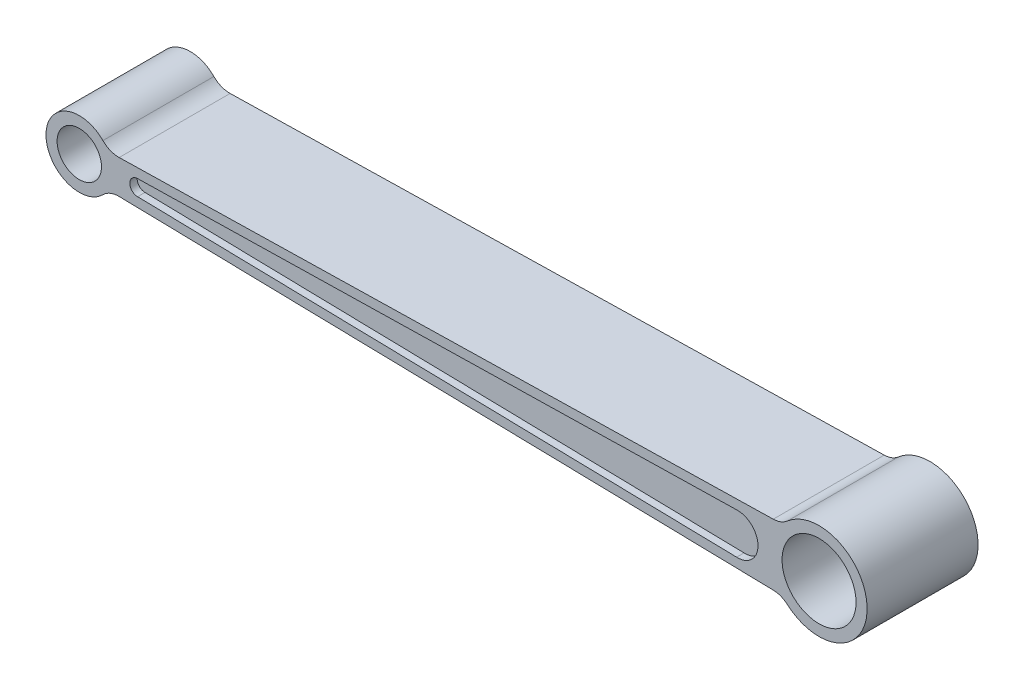
SolidWorks part; units mm, degrees
material "AISI 1020"
ref_plane "Front Plane" through (0, 0, 0) normal (0, 0, 1) x (1, 0, 0)
ref_plane "Top Plane" through (0, 0, 0) normal (0, 1, 0) x (1, 0, 0)
ref_plane "Right Plane" through (0, 0, 0) normal (1, 0, 0) x (0, 0, -1)
sketch "Sketch1" plane through (0, 0, 0) normal (0, 0, 1) x (1, 0, 0)
  line L0 (7.8837, 1.0596) -> (88.9734, 2.7755)
  line L2 (7.8837, -1.0596) -> (88.9734, -2.7755)
  line L5 (3.8971, 2.25) -> (95.0207, 4.1781)
  line L6 (3.8971, -2.25) -> (95.0207, -4.1781)
  circle A0 centre (0, 0) radius 3
  circle A1 centre (0, 0) radius 4.5
  circle A2 centre (100, 0) radius 5
  circle A3 centre (100, 0) radius 6.5
  arc A6 (7.8837, 1.0596) -> (7.8837, -1.0596) centre (7.8837, 0) ccw
  arc A7 (88.856, -2.773) -> (88.856, 2.773) centre (88.9734, 0) ccw
  dimension "D1" = 9
  dimension "D2" = 6
  dimension "D3" = 10
  dimension "D4" = 13
  dimension "D5" = 100
extrude "Boss-Extrude2" add sketch "Sketch1" along normal mid plane 15 contours A3 L5 A1 L6 A7 L2 A6 L0 | A1 A0 | A3 A2 region at (49.4783, 2.2992, 0) region at (4.2237, 1.1317, 0) region at (102.1603, 5.9352, 0)
extrude "Boss-Extrude3" add sketch "Sketch1<7>" along normal mid plane 13 contours L2 A7 L0 A6 region at (55.5485, 0, 0)
sketch "Sketch1<7>" plane through (0, 0, 0) normal (0, 0, 1) x (1, 0, 0) same geometry as "Sketch1"
fillet "Fillet1" radius 3 4 edges at (95.0207, -4.1781, 0) (3.8971, -2.25, 0) (3.8971, 2.25, 0) (95.0207, 4.1781, 0)
